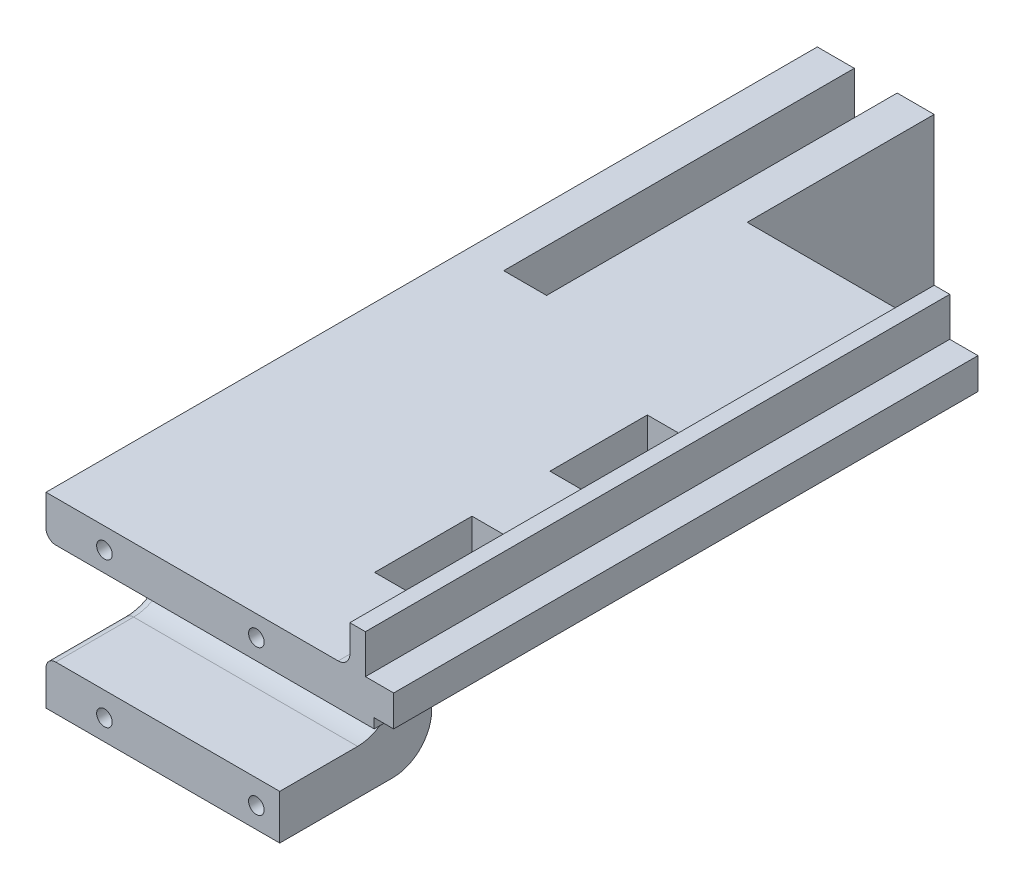
SolidWorks part; units mm, degrees
ref_plane "Alzado" through (0, 0, 0) normal (0, 0, 1) x (1, 0, 0)
ref_plane "Planta" through (0, 0, 0) normal (0, 1, 0) x (1, 0, 0)
ref_plane "Vista lateral" through (0, 0, 0) normal (1, 0, 0) x (0, 0, -1)
sketch "Croquis1" plane through (0, 0, 0) normal (0, 0, 1) x (1, 0, 0)
  line L1 (-66.2162, 31.0113) -> (-6.2162, 31.0113)
  line L2 (-66.2162, 31.0113) -> (-66.2162, -16.9887)
  line L3 (-66.2162, -16.9887) -> (-6.2162, -16.9887)
  line L4 (-6.2162, 31.0113) -> (-6.2162, -16.9887)
  dimension "D1" = 48
  dimension "D2" = 60
extrude "Saliente-Extruir1" add sketch "Croquis1" along normal blind 6
sketch "Croquis4" plane through (0, 0, 6) normal (0, 0, 1) x (1, 0, 0)
  line L0 (-66.2162, 31.0113) -> (-66.2162, 19.5113)
  line L1 (-66.2162, 31.0113) -> (-66.2162, -16.9887) construction
  line L3 (-66.2162, -5.4887) -> (-66.2162, -16.9887)
  line L4 (-66.2162, 31.0113) -> (-6.2162, 31.0113)
  line L6 (-6.2162, 31.0113) -> (-6.2162, 19.5113)
  line L7 (-6.2162, -16.9887) -> (-6.2162, 31.0113) construction
  line L8 (-6.2162, 19.5113) -> (-66.2162, 19.5113)
  line L9 (-66.2162, -5.4887) -> (-6.2162, -5.4887)
  line L10 (-6.2162, -5.4887) -> (-6.2162, -16.9887)
  line L11 (-6.2162, -16.9887) -> (-66.2162, -16.9887)
  dimension "D1" = 25
extrude "Saliente-Extruir3" add sketch "Croquis4" along normal blind 30
sketch "Croquis3" plane through (0, 0, 6) normal (0, 0, 1) x (1, 0, 0)
  circle A0 centre (-51.2162, 25.6613) radius 2.125
  circle A1 centre (-12.2162, 25.6613) radius 2.125
  circle A2 centre (-12.2162, -11.6387) radius 2.125
  circle A3 centre (-51.2162, -11.6387) radius 2.125
  dimension "D7" = 4.25
  dimension "D9" = 4.25
  dimension "D10" = 4.25
  dimension "D2" = 4.25
  dimension "D3" = 37.3
  dimension "D4" = 39
sketch "Croquis5" plane through (0, 0, 36) normal (0, 0, 1) x (1, 0, 0)
  circle A0 centre (-51.2162, 25.6613) radius 2
  circle A1 centre (-12.2162, 25.6613) radius 2
  circle A2 centre (-12.2162, -11.6387) radius 2
  circle A3 centre (-51.2162, -11.6387) radius 2
  dimension "D1" = 4
  dimension "D2" = 4
  dimension "D3" = 4
  dimension "D4" = 4
extrude "Cortar-Extruir3" cut sketch "Croquis5" against normal blind 16
sketch "Croquis6" plane through (0, 0, 0) normal (0, 0, -1) x (-1, 0, 0)
  line L0 (66.2162, -16.9887) -> (6.2162, -16.9887) construction
  line L1 (66.2162, 31.0113) -> (36.2162, 31.0113)
  line L2 (66.2162, 31.0113) -> (66.2162, -16.9887)
  line L3 (66.2162, -16.9887) -> (36.2162, -16.9887)
  line L4 (36.2162, 31.0113) -> (36.2162, -16.9887)
  dimension "D1" = 30
extrude "Saliente-Extruir4" add sketch "Croquis6" along normal blind 162
sketch "Croquis7" plane through (0, 0, -162) normal (0, 0, -1) x (-1, 0, 0)
  circle A0 centre (51.2162, 7.0113) radius 2
  dimension "D1" = 4
extrude "Cortar-Extruir4" cut sketch "Croquis7" against normal blind 16
sketch "Croquis8" plane through (0, 0, -162) normal (0, 0, -1) x (-1, 0, 0)
  line L0 (41.2162, 12.0113) -> (41.2162, 9.5131)
  line L10 (36.2162, 12.0113) -> (41.2162, 12.0113)
  line L11 (36.2162, 12.0113) -> (36.2162, 2.0113)
  line L12 (36.2162, 2.0113) -> (41.2162, 2.0113)
  line L21 (41.2162, 9.5131) -> (44.2162, 9.5131)
  line L23 (41.2162, 4.5131) -> (44.2162, 4.5131)
  line L24 (44.2162, 9.5131) -> (44.2162, 4.5131)
  line L25 (41.2162, 2.0113) -> (41.2162, 4.5131)
  dimension "D1" = 5
  dimension "D2" = 3
  dimension "D3" = 5
sketch "Croquis11" plane through (-36.2162, 0, 0) normal (1, 0, 0) x (0, 0, -1)
  line L1 (-36, 19.5113) -> (-36, 31.0113) construction
  line L4 (-36, 19.5113) -> (-36, 31.0113)
  line L6 (-36, 19.5113) -> (114, 19.5113)
  line L7 (114, 19.5113) -> (114, 31.0113)
  line L8 (162, 31.0113) -> (0, 31.0113) construction
  line L9 (162, 31.0113) -> (0, 31.0113) construction
  line L10 (-36, 31.0113) -> (114, 31.0113)
  dimension "D1" = 150
extrude "Saliente-Extruir6" add sketch "Croquis11" along normal blind 59.25
sketch "Croquis12" plane through (0, 31.0113, 0) normal (0, 1, 0) x (1, 0, 0)
  line L0 (23.0338, -36) -> (-66.2162, -36) construction
  line L1 (15.7838, -36) -> (11.7838, -36)
  line L2 (-66.2162, -36) -> (-66.2162, 162) construction
  line L3 (-66.2162, -36) -> (-66.2162, 162) construction
  line L4 (15.7838, -36) -> (15.7838, 114)
  line L5 (15.7838, 114) -> (11.7838, 114)
  line L6 (23.0338, 114) -> (-36.2162, 114) construction
  line L7 (11.7838, 114) -> (11.7838, -36)
  dimension "D1" = 82
  dimension "D2" = 150
  dimension "D3" = 4
extrude "Saliente-Extruir7" add sketch "Croquis12" along normal blind 10
sketch "Croquis14" plane through (0, 0, -114) normal (0, 0, -1) x (-1, 0, 0)
  line L0 (-23.0338, 23.0113) -> (-18.0338, 23.0113)
  line L1 (-18.0338, 23.0113) -> (-18.0338, 19.5113)
  line L2 (-23.0338, 23.0113) -> (-23.0338, 19.5113)
  line L3 (-23.0338, 19.5113) -> (-18.0338, 19.5113)
  line L4 (36.2162, 19.5113) -> (36.2162, 31.0113)
  line L5 (36.2162, 31.0113) -> (-11.7838, 31.0113)
  line L6 (-23.0338, 31.0113) -> (-23.0338, 19.5113)
  line L7 (-23.0338, 19.5113) -> (36.2162, 19.5113)
  line L8 (36.2162, 19.5113) -> (36.2162, 31.0113) construction
  line L9 (36.2162, 31.0113) -> (-11.7838, 31.0113) construction
  line L10 (-23.0338, 31.0113) -> (-23.0338, 19.5113) construction
  line L11 (-23.0338, 19.5113) -> (36.2162, 19.5113) construction
  line L20 (-11.7838, 31.0113) -> (-11.7838, 41.0113)
  line L22 (-11.7838, 41.0113) -> (-15.7838, 41.0113)
  line L24 (-15.7838, 41.0113) -> (-15.7838, 31.0113)
  line L26 (-15.7838, 31.0113) -> (-23.0338, 31.0113)
  line L27 (-15.7838, 31.0113) -> (-23.0338, 31.0113) construction
  dimension "D2" = 5
  dimension "D3" = 8
  dimension "D1" = 0
extrude "Cortar-Extruir6" cut sketch "Croquis14" against normal through all both and the other way through all
sketch "Croquis15" plane through (0, 0, -162) normal (0, 0, -1) x (-1, 0, 0)
  line L0 (51.2162, 45.0729) -> (51.2162, 16.9496) construction
  line L1 (56.7162, 20.0113) -> (45.7162, 20.0113)
  line L2 (45.7162, 20.0113) -> (45.7162, 31.0113)
  line L3 (56.7162, 20.0113) -> (56.7162, 31.0113)
  line L4 (66.2162, -16.9887) -> (66.2162, 31.0113)
  line L5 (66.2162, 31.0113) -> (36.2162, 31.0113)
  line L6 (36.2162, 31.0113) -> (36.2162, -16.9887)
  line L7 (36.2162, -16.9887) -> (66.2162, -16.9887)
  line L8 (66.2162, -16.9887) -> (66.2162, 31.0113) construction
  line L9 (66.2162, 31.0113) -> (36.2162, 31.0113) construction
  line L10 (56.7162, 31.0113) -> (45.7162, 31.0113)
  point P6 (51.2162, 31.0113)
  point P10 (51.2162, 20.0113)
  dimension "D2" = 11
  dimension "D3" = 11
  dimension "D1" = 0
extrude "Cortar-Extruir7" cut sketch "Croquis15" against normal blind 90 and the other way through all
sketch "Croquis16" plane through (-66.2162, 0, 0) normal (-1, 0, 0) x (0, 0, 1)
  line L0 (6, 19.5113) -> (6, 20.5113)
  line L1 (6, 20.5113) -> (36, 20.5113)
  line L2 (36, 31.0113) -> (36, 19.5113) construction
  line L3 (6, 19.5113) -> (36, 19.5113)
  line L4 (36, 19.5113) -> (36, 20.5113)
  dimension "D1" = 1
extrude "Cortar-Extruir10" cut sketch "Croquis16" against normal through all contours L1 L4 L3 L0
fillet "Redondeo1" radius 10 2 edges at (-36.2162, -5.4887, 6) (-24.0912, 20.5113, 6)
sketch "Croquis20" plane through (0, 0, 0) normal (0, 0, -1) x (-1, 0, 0)
  line L1 (6.2162, 19.5113) -> (36.2162, 19.5113)
  line L2 (6.2162, 19.5113) -> (6.2162, -16.9887)
  line L3 (6.2162, -16.9887) -> (36.2162, -16.9887)
  line L4 (36.2162, 19.5113) -> (36.2162, -16.9887)
extrude "Saliente-Extruir8" add sketch "Croquis20" along normal blind 50
sketch "Croquis21" plane through (0, 19.5113, 0) normal (0, -1, 0) x (1, 0, 0)
  line L1 (2.7838, 11.6411) -> (-6.2162, 11.6411)
  line L2 (2.7838, 11.6411) -> (2.7838, -13.3589)
  line L3 (2.7838, -13.3589) -> (-6.2162, -13.3589)
  line L4 (-6.2162, 11.6411) -> (-6.2162, -13.3589)
  line L5 (18.0338, 11.6411) -> (-6.2162, 11.6411) construction
  line L6 (-6.2162, 36) -> (-6.2162, -50) construction
  line L12 (-1.7162, 23.4456) -> (-1.7162, -75.1671) construction
  line L13 (2.7838, -33.3589) -> (2.7838, -58.3589)
  line L14 (2.7838, -33.3589) -> (-6.2162, -33.3589)
  line L15 (-6.2162, -33.3589) -> (-6.2162, -58.3589)
  line L16 (2.7838, -58.3589) -> (-6.2162, -58.3589)
  point P10 (-1.7162, -13.3589)
  dimension "D1" = 9
  dimension "D2" = 25
  dimension "D3" = 2
  dimension "D4" = 20
extrude "Cortar-Extruir11" cut sketch "Croquis21" against normal blind 40
sketch "Croquis22" plane through (0, 0, -50) normal (0, 0, -1) x (-1, 0, 0)
  line L1 (36.2162, 19.5113) -> (6.2162, 19.5113)
  line L2 (36.2162, 19.5113) -> (36.2162, -16.9887)
  line L3 (36.2162, -16.9887) -> (6.2162, -16.9887)
  line L4 (6.2162, 19.5113) -> (6.2162, -16.9887)
extrude "Cortar-Extruir13" cut sketch "Croquis22" against normal blind 47
fillet "Redondeo3" radius 10 1 edges at (-21.2162, -16.9887, -3)
sketch "Croquis23" plane through (0, 0, 36) normal (0, 0, 1) x (1, 0, 0)
  circle A0 centre (-12.2162, -11.6387) radius 2 construction
  circle A1 centre (-51.2162, -11.6387) radius 2 construction
  circle A2 centre (-12.2162, 25.6613) radius 2 construction
  circle A3 centre (-51.2162, 25.6613) radius 2 construction
  circle A4 centre (-12.2162, -11.6387) radius 2
  circle A5 centre (-51.2162, -11.6387) radius 2
  circle A6 centre (-12.2162, 25.6613) radius 2
  circle A7 centre (-51.2162, 25.6613) radius 2
extrude "Cortar-Extruir14" cut sketch "Croquis23" against normal blind 16
fillet "Redondeo4" radius 3 1 edges at (11.7838, 31.0113, -39)
sketch "Croquis24" plane through (0, 0, -162) normal (0, 0, -1) x (-1, 0, 0)
  line L0 (36.2162, -16.9887) -> (66.2162, -16.9887) construction
  line L1 (36.2162, -16.9887) -> (66.2162, -16.9887) construction
  line L2 (51.2162, 1.6971) -> (51.2162, -35.6746) construction
  line L3 (48.6162, -16.9887) -> (48.6162, -12.9887)
  line L4 (48.6162, -12.9887) -> (44.2162, -12.9887)
  line L5 (44.2162, -12.9887) -> (44.2162, -8.9887)
  line L6 (44.2162, -8.9887) -> (58.2162, -8.9887)
  line L7 (48.6162, -16.9887) -> (53.8162, -16.9887)
  line L8 (58.2162, -12.9887) -> (58.2162, -8.9887)
  line L9 (53.8162, -12.9887) -> (58.2162, -12.9887)
  line L10 (53.8162, -16.9887) -> (53.8162, -12.9887)
  point P5 (51.2162, -16.9887)
  point P12 (51.2162, -16.9887)
  point P13 (51.2162, -8.9887)
  dimension "D1" = 4
  dimension "D2" = 4
  dimension "D3" = 7
  dimension "D4" = 2.6
extrude "Cortar-Extruir15" cut sketch "Croquis24" against normal blind 170
fillet "Redondeo5" radius 6 1 edges at (-36.2162, 19.5113, -58.5)
fillet "Redondeo6" radius 2.5 5 edges at (-66.2162, 20.5113, 26) (-66.2162, 17.5823, 8.9289) (-66.2162, 7.5113, 6) (-66.2162, -2.5598, 8.9289) (-66.2162, -5.4887, 26)
